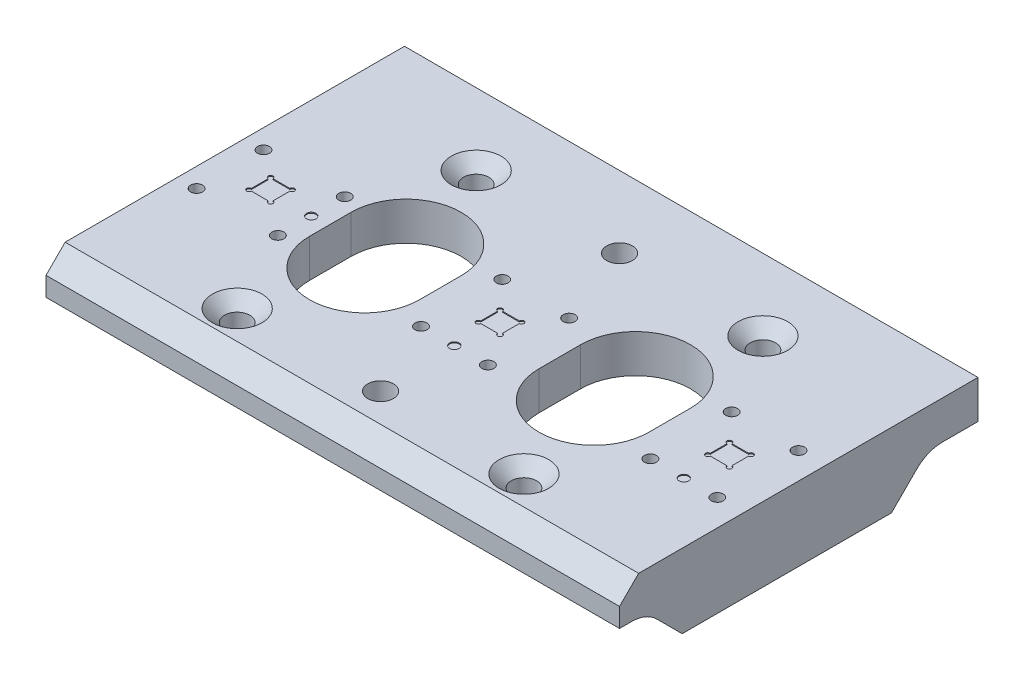
SolidWorks part; units mm, degrees
material "6061 Сплав"
ref_plane "Спереди" through (0, 0, 0) normal (0, 0, 1) x (1, 0, 0)
ref_plane "Сверху" through (0, 0, 0) normal (0, 1, 0) x (1, 0, 0)
ref_plane "Справа" through (0, 0, 0) normal (1, 0, 0) x (0, 0, -1)
sketch "Эскиз5" plane through (0, 0, 0) normal (0, 1, 0) x (1, 0, 0)
  line L1 (0, -35) -> (120, -35)
  line L2 (0, -35) -> (0, 40)
  line L3 (0, 40) -> (120, 40)
  line L4 (120, -35) -> (120, 40)
  line L5 (0, -35) -> (120, 40) construction
  line L6 (0, 40) -> (120, -35) construction
extrude "Бобышка-Вытянуть2" add sketch "Эскиз5" against normal blind 8
ref_axis "Ось1" through (120, 0, -2.5) along (-1, 0, 0)
sketch "Sketch2" plane through (0, 0, 0) normal (0, 1, 0) x (1, 0, 0)
  line L0 (40, 40) -> (40, -35) construction
  line L1 (106.24, -2.26) -> (109.76, -2.26)
  line L2 (58.24, -2.26) -> (61.76, -2.26)
  line L3 (57.74, -1.76) -> (57.74, 1.76)
  line L4 (58.24, 2.26) -> (61.76, 2.26)
  line L5 (62.26, -1.76) -> (62.26, 1.76)
  line L6 (57.74, -2.26) -> (62.26, 2.26) construction
  line L7 (0, 40) -> (120, 40) construction
  line L8 (0, -35) -> (120, -35) construction
  line L9 (80, 40) -> (80, -35) construction
  line L11 (10.24, -2.26) -> (13.76, -2.26)
  line L12 (105.74, -1.76) -> (105.74, 1.76)
  line L13 (106.24, 2.26) -> (109.76, 2.26)
  line L14 (110.26, -1.76) -> (110.26, 1.76)
  line L15 (105.74, -2.26) -> (110.26, 2.26) construction
  line L16 (105.74, 2.26) -> (110.26, -2.26) construction
  line L18 (9.74, -1.76) -> (9.74, 1.76)
  line L19 (10.24, 2.26) -> (13.76, 2.26)
  line L20 (14.26, -1.76) -> (14.26, 1.76)
  line L21 (9.74, -2.26) -> (14.26, 2.26) construction
  line L22 (9.74, 2.26) -> (14.26, -2.26) construction
  line L23 (57.74, 2.26) -> (62.26, -2.26) construction
  circle A0 centre (59.481, -9.027) radius 1
  circle A1 centre (21.027, -0.519) radius 1
  circle A2 centre (107.481, -9.027) radius 1
  arc A3 (14.26, 1.76) -> (13.76, 2.26) centre (14.26, 2.26) ccw
  arc A4 (10.24, 2.26) -> (9.74, 1.76) centre (9.74, 2.26) ccw
  arc A5 (9.74, -1.76) -> (10.24, -2.26) centre (9.74, -2.26) ccw
  arc A6 (13.76, -2.26) -> (14.26, -1.76) centre (14.26, -2.26) ccw
  arc A7 (57.74, -1.76) -> (58.24, -2.26) centre (57.74, -2.26) ccw
  arc A8 (61.76, -2.26) -> (62.26, -1.76) centre (62.26, -2.26) ccw
  arc A9 (62.26, 1.76) -> (61.76, 2.26) centre (62.26, 2.26) ccw
  arc A10 (58.24, 2.26) -> (57.74, 1.76) centre (57.74, 2.26) ccw
  arc A11 (110.26, 1.76) -> (109.76, 2.26) centre (110.26, 2.26) ccw
  arc A12 (106.24, 2.26) -> (105.74, 1.76) centre (105.74, 2.26) ccw
  arc A13 (109.76, -2.26) -> (110.26, -1.76) centre (110.26, -2.26) ccw
  arc A14 (105.74, -1.76) -> (106.24, -2.26) centre (105.74, -2.26) ccw
  point P0 (60, 0)
  point P1 (60, 0)
  point P2 (60, 0)
  point P5 (60, 0)
  point P6 (60, 0)
  point P7 (59.481, -9.027)
  point P8 (66.481, -9.027)
  point P9 (52.481, -9.027)
  point P10 (52.481, 7.973)
  point P11 (66.481, 7.973)
  point P23 (12, 0)
  point P24 (12, 0)
  point P25 (12, 0)
  point P28 (12, 0)
  point P29 (12, 0)
  point P30 (21.027, -0.519)
  point P31 (108, 0)
  point P32 (108, 0)
  point P33 (108, 0)
  point P36 (108, 0)
  point P37 (108, 0)
  point P38 (107.481, -9.027)
  point P39 (114.481, -9.027)
  point P40 (100.481, -9.027)
  point P41 (100.481, 7.973)
  point P42 (114.481, 7.973)
  point P46 (21.027, 6.481)
  point P47 (21.027, -7.519)
  point P48 (4.027, -7.519)
  point P49 (4.027, 6.481)
  dimension "D19" = 4.52
  dimension "D37" = 0.5
  dimension "D38" = 1
  dimension "D39" = 1
  dimension "D1" = 9.027
  dimension "D2" = 7.973
  dimension "D3" = 6.481
  dimension "D4" = 7.519
  dimension "D5" = 7.973
  dimension "D6" = 9.027
  dimension "D7" = 7.519
  dimension "D8" = 6.481
  dimension "D9" = 7
  dimension "D10" = 9.027
  dimension "D11" = 6.481
  dimension "D12" = 7.519
  dimension "D13" = 7.973
  dimension "D14" = 9.027
  dimension "D15" = 7.519
  dimension "D16" = 6.481
  dimension "D17" = 9.027
  dimension "D18" = 7.973
  dimension "D20" = 4.52
  dimension "D21" = 6.481
  dimension "D22" = 7.519
  dimension "D23" = 7.973
  dimension "D24" = 9.027
  dimension "D25" = 7.519
  dimension "D26" = 6.481
  dimension "D27" = 9.027
  dimension "D28" = 7.973
  dimension "D29" = 9.027
  dimension "D30" = 7
  dimension "D31" = 4.52
  dimension "D32" = 4.52
  dimension "D33" = 4.52
  dimension "D34" = 4.52
  dimension "D35" = 9.027
  dimension "D36" = 7
extrude "Cut-Extrude2" cut sketch "Sketch2" against normal blind 0.2
hole_wizard "M3x0.5 Tapped Hole1" positions "Sketch4" profile "Sketch3" tap size "M3x0.5" standard "ANSI Metric"
sketch "Sketch4" plane through (0, 0, 0) normal (0, 1, 0) x (1, 0, 0)
  point P0 (21.027, 6.481)
  point P3 (4.027, 6.481)
  point P6 (4.027, -7.519)
  point P9 (21.027, -7.519)
  point P12 (52.481, 7.973)
  point P15 (66.481, 7.973)
  point P18 (66.481, -9.027)
  point P21 (52.481, -9.027)
  point P24 (100.481, -9.027)
  point P27 (114.481, -9.027)
  point P30 (114.481, 7.973)
  point P33 (100.481, 7.973)
sketch "Sketch3" plane through (21.027, 0, -6.481) normal (1, 0, 0) x (0, 0, 1)
  line L0 (0, 0) -> (0, 6.2511)
  line L1 (0, 6.2511) -> (1.25, 5.5)
  line L2 (1.25, 5.5) -> (1.25, 0)
  line L5 (1.25, 0) -> (0, 0)
  line L10 (0, 6.2511) -> (-1.25, 5.5) construction
  line L11 (0, -6.35) -> (0, 107.95) construction
  dimension "Tap Drill Dia." = 2.5
  dimension "Tap Drill Depth" = 5.5
  dimension "Drill Angle" = 118
cosmetic thread "Hole Thread1" parameters "D1"=4, "D2"=3
cosmetic thread "Hole Thread2" parameters "D1"=4, "D2"=3
cosmetic thread "Hole Thread3" parameters "D1"=4, "D2"=3
cosmetic thread "Hole Thread4" parameters "D1"=4, "D2"=3
cosmetic thread "Hole Thread5" parameters "D1"=4, "D2"=3
cosmetic thread "Hole Thread6" parameters "D1"=4, "D2"=3
cosmetic thread "Hole Thread7" parameters "D1"=4, "D2"=3
cosmetic thread "Hole Thread8" parameters "D1"=4, "D2"=3
cosmetic thread "Hole Thread9" parameters "D1"=4, "D2"=3
cosmetic thread "Hole Thread10" parameters "D1"=4, "D2"=3
cosmetic thread "Hole Thread11" parameters "D1"=4, "D2"=3
cosmetic thread "Hole Thread12" parameters "D1"=4, "D2"=3
sketch "Sketch6" plane through (0, 0, 0) normal (0, 1, 0) x (1, 0, 0)
  line L1 (0, 40) -> (0, -35) construction
  line L2 (0, 6) -> (120, 6) construction
  line L3 (120, -35) -> (120, 40) construction
  line L4 (0, -6) -> (120, -6) construction
  point P11 (36, 6)
  point P12 (60, 6)
  point P13 (84, 6)
  point P16 (84, -6)
  point P17 (60, -6)
  point P18 (36, -6)
sketch "Sketch9" plane through (0, 0, 0) normal (0, 1, 0) x (1, 0, 0)
  line L1 (30, -25) -> (90, -25) construction
  line L2 (30, -25) -> (30, 25) construction
  line L3 (30, 25) -> (90, 25) construction
  line L4 (90, -25) -> (90, 25) construction
  line L5 (30, -25) -> (90, 25) construction
  line L6 (30, 25) -> (90, -25) construction
  point P0 (60, 0)
  point P1 (60, 0)
  point P7 (90, 25)
  point P8 (90, -25)
  point P9 (30, -25)
  point P10 (30, 25)
sketch "Sketch5" plane through (0, -8, 0) normal (0, -1, 0) x (1, 0, 0)
  line L0 (-60, 0) -> (180, 0) construction
  line L1 (60, 28.028) -> (60, -31.0562) construction
  line L3 (30, -25) -> (90, -25) construction
  line L4 (30, 25) -> (90, 25) construction
  circle A1 centre (60, 25) radius 2.6
  circle A4 centre (60, -25) radius 2.6
  point P5 (60, 25)
  point P6 (60, -25)
  point P7 (60, 25)
  point P8 (60, 0)
  point P16 (60, -25)
hole_wizard "Зенковка для  винта с плоской головкой M51" positions "Sketch11" profile "Sketch10" countersink size "M5" standard "Ansi Metric" end condition through all
sketch "Sketch11" plane through (0, 0, 0) normal (0, 1, 0) x (1, 0, 0)
  point P0 (30, 25)
  point P3 (90, 25)
  point P6 (90, -25)
  point P9 (30, -25)
sketch "Sketch10" plane through (30, 0, -25) normal (1, 0, 0) x (0, 0, 1)
  line L0 (0, 0) -> (0, 8)
  line L1 (0, 8) -> (2.65, 8)
  line L2 (2.65, 8) -> (2.65, 2.55)
  line L3 (2.65, 2.55) -> (5.2, 0)
  line L5 (5.2, 0) -> (0, 0)
  line L6 (-2.65, 2.55) -> (-5.2, 0) construction
  line L11 (0, -6.35) -> (0, 107.95) construction
  dimension "Thru Hole Dia." = 5.3
  dimension "Thru Hole Depth" = 8
  dimension "Near C'Sink Dia." = 10.4
  dimension "Near C'Sink Angle" = 90
extrude "Cut-Extrude3" cut sketch "Sketch5" against normal through all draft 0.573 draft outward yes
sketch "Эскиз6" plane through (0, 0, 0) normal (0, 1, 0) x (1, 0, 0)
  line L21 (84, 4.3542) -> (84, -4.3542) construction
  line L22 (95.5, 4.3542) -> (95.5, -4.3542)
  line L25 (72.5, 4.3542) -> (72.5, -4.3542)
  line L26 (36, 4.3542) -> (36, -4.3542) construction
  line L27 (47.5, 4.3542) -> (47.5, -4.3542)
  line L28 (24.5, 4.3542) -> (24.5, -4.3542)
  line L31 (24.5, 12.9971) -> (24.5, -11.3481) construction
  line L32 (95.5, 13.6564) -> (95.5, -12.527) construction
  line L33 (72.5, 14.923) -> (72.5, -13.3148) construction
  line L34 (47.5, 13.6564) -> (47.5, -14.0778) construction
  circle A0 centre (30, 25) radius 10 construction
  circle A1 centre (60, 25) radius 10 construction
  circle A2 centre (90, 25) radius 10 construction
  circle A3 centre (30, -25) radius 10 construction
  circle A4 centre (60, -25) radius 10 construction
  circle A5 centre (90, -25) radius 10 construction
  arc A6 (95.5, 4.3542) -> (72.5, 4.3542) centre (84, 4.3542) ccw
  arc A7 (72.5, -4.3542) -> (95.5, -4.3542) centre (84, -4.3542) ccw
  arc A8 (47.5, 4.3542) -> (24.5, 4.3542) centre (36, 4.3542) ccw
  arc A9 (24.5, -4.3542) -> (47.5, -4.3542) centre (36, -4.3542) ccw
  point P0 (60, 25)
  point P6 (60, -25)
  point P18 (4.027, -7.519)
  point P24 (114.481, 7.973)
  point P30 (114.481, -9.027)
  point P66 (84, 0)
  point P71 (36, 0)
  dimension "D1" = 12.5
  dimension "D2" = 12.5
  dimension "D3" = 12.5
  dimension "D4" = 12.5
extrude "Вырез-Вытянуть1" cut sketch "Эскиз6" against normal blind 10
sketch "Эскиз7" plane through (0, 0, 0) normal (-1, 0, 0) x (0, 0, 1)
  line L0 (-40, -8) -> (35, -8) construction
  line L1 (0, 11.4102) -> (0, -23.4367) construction
  line L2 (-32.5, -15.5) -> (32.5, -15.5) construction
  line L3 (-32.5, -8) -> (32.5, -8)
  line L4 (-21.8934, -15.5) -> (-27.1967, -10.1967)
  line L5 (27.1967, -10.1967) -> (21.8934, -15.5)
  line L6 (-21.8934, -15.5) -> (21.8934, -15.5)
  arc A0 (-27.1967, -10.1967) -> (-32.5, -8) centre (-32.5, -15.5) ccw
  arc A1 (32.5, -8) -> (27.1967, -10.1967) centre (32.5, -15.5) ccw
  point P8 (0, -15.5)
  point P16 (0, -15.5)
  dimension "D2" = 15
  dimension "D1" = 65
  dimension "D3" = 45
  dimension "D4" = 7.5
extrude "Бобышка-Вытянуть3" add sketch "Эскиз7" against normal through all
sketch "Эскиз8" plane through (0, 0, 35) normal (0, 0, 1) x (1, 0, 0)
  line L0 (0, -8) -> (120, -8) construction
  line L1 (14, -39.1754) -> (106, -39.1754)
  line L2 (14, -39.1754) -> (14, -8)
  line L3 (14, -8) -> (106, -8)
  line L4 (106, -39.1754) -> (106, -8)
  line L5 (0, -8) -> (0, 0) construction
  line L6 (120, -8) -> (120, 0) construction
  dimension "D1" = 14
  dimension "D2" = 14
extrude "Вырез-Вытянуть2" cut sketch "Эскиз8" against normal through all
chamfer "Фаска1" distance 4 angle 45 1 edges at (60, 0, 35)
